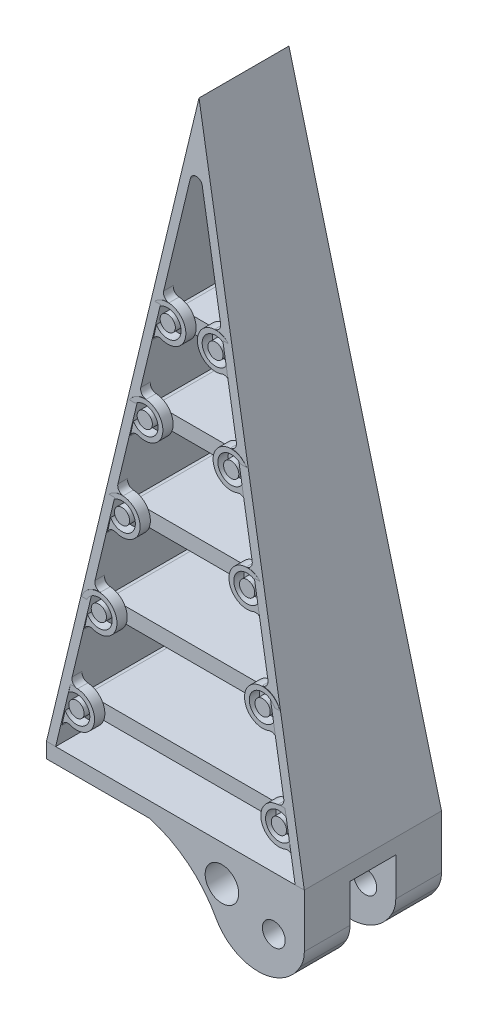
SolidWorks part; units mm, degrees
ref_plane "Ebene vorne" through (0, 0, 0) normal (0, 0, 1) x (1, 0, 0)
ref_plane "Ebene oben" through (0, 0, 0) normal (0, 1, 0) x (1, 0, 0)
ref_plane "Ebene rechts" through (0, 0, 0) normal (1, 0, 0) x (0, 0, -1)
ref_plane "Ebene7" through (0, 0, 9) normal (0, 0, 1) x (1, 0, 0)
ref_plane "Ebene8" through (17, 0, 0) normal (1, 0, 0) x (0, 0, -1)
sketch "Skizze1" plane through (0, 0, 0) normal (0, 0, 1) x (1, 0, 0)
  line L0 (0, 0) -> (16.9111, -80)
  line L1 (16.9111, -80) -> (15.7111, -80)
  line L2 (15.7111, -80) -> (0, -5.6767)
  line L3 (0, -5.6767) -> (-15.7111, -80)
  line L4 (-15.7111, -80) -> (-16.9111, -80)
  line L5 (-16.9111, -80) -> (0, 0)
  point P2 (-16.3111, -80)
  dimension "D1" = 1.2
  dimension "D2" = 1.2
  dimension "D3" = 23.872
  dimension "D4" = 80
extrude "Aufsatz-Linear austragen4" add sketch "Skizze1" along normal blind 18
sketch "Skizze11" plane through (17, 0, 0) normal (1, 0, 0) x (0, 0, -1)
  line L0 (-18, -80) -> (-14.9, 0)
  line L1 (-18, 0) -> (0, 0) construction
  line L2 (-14.9, 0) -> (-18, 0)
  line L3 (-18, 0) -> (-18, -80)
  line L4 (0, -80) -> (-3.1, 0)
  line L5 (-3.1, 0) -> (0, 0)
  line L6 (0, 0) -> (0, -80)
  dimension "D1" = 3.1
  dimension "D2" = 3.1
extrude "Schnitt-Linear austragen1" cut sketch "Skizze11" against normal through all
sketch "Skizze6" plane through (0, 0, 9) normal (0, 0, 1) x (1, 0, 0)
  line L1 (0, -5.6767) -> (-15.7111, -80) construction
  line L2 (15.7111, -80) -> (0, -5.6767) construction
  line L8 (3.1325, -25.6767) -> (-3.1325, -25.6767)
  line L11 (-3.1325, -27.6767) -> (3.1325, -27.6767)
  arc A0 (-3.1325, -25.6767) -> (-3.1325, -27.6767) centre (-3.1325, -26.6767) ccw
  arc A1 (3.1325, -25.6767) -> (3.1325, -27.6767) centre (3.1325, -26.6767) cw
  point P4 (-4.1325, -26.6767)
  point P9 (4.1325, -26.6767)
  dimension "D3" = 0.3
  dimension "D1" = 20
  dimension "D2" = 2
  dimension "D4" = 0.3
extrude "Aufsatz-Linear austragen5" add sketch "Skizze6" along normal blind 5.37 and the other way blind 5.37
sketch "Skizze7" plane through (0, 0, 9) normal (0, 0, 1) x (1, 0, 0)
  line L9 (5.6692, -37.6767) -> (-5.6692, -37.6767)
  line L12 (-5.6692, -39.6767) -> (5.6692, -39.6767)
  line L13 (-3.1325, -27.6767) -> (3.1325, -27.6767) construction
  line L14 (0, -5.6767) -> (-15.7111, -80) construction
  line L15 (15.7111, -80) -> (0, -5.6767) construction
  arc A0 (-5.6692, -37.6767) -> (-5.6692, -39.6767) centre (-5.6692, -38.6767) ccw
  arc A1 (5.6692, -37.6767) -> (5.6692, -39.6767) centre (5.6692, -38.6767) cw
  point P3 (-6.6692, -38.6767)
  point P10 (6.6692, -38.6767)
  dimension "D3" = 0.3
  dimension "D1" = 10
  dimension "D2" = 2
  dimension "D4" = 0.3
extrude "Aufsatz-Linear austragen6" add sketch "Skizze7" along normal blind 5.85 and the other way blind 5.85
sketch "Skizze8" plane through (0, 0, 9) normal (0, 0, 1) x (1, 0, 0)
  line L9 (8.2059, -49.6767) -> (-8.2059, -49.6767)
  line L12 (-8.2059, -51.6767) -> (8.2059, -51.6767)
  line L13 (-5.6692, -39.6767) -> (5.6692, -39.6767) construction
  line L14 (0, -5.6767) -> (-15.7111, -80) construction
  line L15 (15.7111, -80) -> (0, -5.6767) construction
  arc A0 (-8.2059, -49.6767) -> (-8.2059, -51.6767) centre (-8.2059, -50.6767) ccw
  arc A1 (8.2059, -49.6767) -> (8.2059, -51.6767) centre (8.2059, -50.6767) cw
  point P6 (-9.2059, -50.6767)
  point P11 (9.2059, -50.6767)
  dimension "D3" = 0.3
  dimension "D1" = 10
  dimension "D2" = 2
  dimension "D4" = 0.3
extrude "Aufsatz-Linear austragen7" add sketch "Skizze8" along normal blind 6.3 and the other way blind 6.3
sketch "Skizze9" plane through (0, 0, 9) normal (0, 0, 1) x (1, 0, 0)
  line L9 (10.7426, -61.6767) -> (-10.7426, -61.6767)
  line L12 (-10.7426, -63.6767) -> (10.7426, -63.6767)
  line L13 (-8.2059, -51.6767) -> (8.2059, -51.6767) construction
  line L14 (0, -5.6767) -> (-15.7111, -80) construction
  line L15 (15.7111, -80) -> (0, -5.6767) construction
  arc A0 (-10.7426, -61.6767) -> (-10.7426, -63.6767) centre (-10.7426, -62.6767) ccw
  arc A1 (10.7426, -61.6767) -> (10.7426, -63.6767) centre (10.7426, -62.6767) cw
  point P3 (-11.7426, -62.6767)
  point P10 (11.7426, -62.6767)
  dimension "D3" = 0.3
  dimension "D1" = 10
  dimension "D2" = 2
  dimension "D4" = 0.3
extrude "Aufsatz-Linear austragen8" add sketch "Skizze9" along normal blind 6.8 and the other way blind 6.8
sketch "Skizze10" plane through (0, 0, 9) normal (0, 0, 1) x (1, 0, 0)
  line L9 (13.2792, -73.6767) -> (-13.2792, -73.6767)
  line L12 (-13.2792, -75.6767) -> (13.2792, -75.6767)
  line L13 (-10.7426, -63.6767) -> (10.7426, -63.6767) construction
  line L14 (0, -5.6767) -> (-15.7111, -80) construction
  line L15 (15.7111, -80) -> (0, -5.6767) construction
  arc A0 (-13.2792, -73.6767) -> (-13.2792, -75.6767) centre (-13.2792, -74.6767) ccw
  arc A1 (13.2792, -73.6767) -> (13.2792, -75.6767) centre (13.2792, -74.6767) cw
  point P3 (-14.2792, -74.6767)
  point P10 (14.2792, -74.6767)
  dimension "D3" = 0.3
  dimension "D1" = 10
  dimension "D2" = 2
  dimension "D4" = 0.3
extrude "Aufsatz-Linear austragen9" add sketch "Skizze10" along normal blind 7.2 and the other way blind 7.2
sketch "Skizze13" plane through (0, 0, 14.37) normal (0, 0, 1) x (1, 0, 0)
  circle A0 centre (-3.1325, -26.6767) radius 1
  circle A1 centre (3.1325, -26.6767) radius 1
  dimension "D1" = 2
  dimension "D2" = 2
extrude "Aufsatz-Linear austragen12" add sketch "Skizze13" along normal blind 1.5
sketch "Skizze15" plane through (0, 0, 15.3) normal (0, 0, 1) x (1, 0, 0)
  circle A0 centre (-8.2059, -50.6767) radius 1
  circle A1 centre (8.2059, -50.6767) radius 1
extrude "Aufsatz-Linear austragen14" add sketch "Skizze15" along normal blind 1.5
sketch "Skizze14" plane through (0, 0, 14.85) normal (0, 0, 1) x (1, 0, 0)
  circle A0 centre (-5.6692, -38.6767) radius 1
  circle A1 centre (5.6692, -38.6767) radius 1
extrude "Aufsatz-Linear austragen13" add sketch "Skizze14" along normal blind 1.5
sketch "Skizze16" plane through (0, 0, 15.8) normal (0, 0, 1) x (1, 0, 0)
  circle A0 centre (-10.7426, -62.6767) radius 1
  circle A1 centre (10.7426, -62.6767) radius 1
extrude "Aufsatz-Linear austragen15" add sketch "Skizze16" along normal blind 1.5
sketch "Skizze17" plane through (0, 0, 16.2) normal (0, 0, 1) x (1, 0, 0)
  circle A0 centre (-13.2792, -74.6767) radius 1
  circle A1 centre (13.2792, -74.6767) radius 1
extrude "Aufsatz-Linear austragen16" add sketch "Skizze17" along normal blind 1.5
sketch "Skizze18" plane through (0, 0, 3.63) normal (0, 0, -1) x (-1, 0, 0)
  circle A0 centre (-3.1325, -26.6767) radius 1
  circle A1 centre (3.1325, -26.6767) radius 1
extrude "Aufsatz-Linear austragen17" add sketch "Skizze18" along normal blind 1.5
sketch "Skizze19" plane through (0, 0, 3.15) normal (0, 0, -1) x (-1, 0, 0)
  circle A0 centre (-5.6692, -38.6767) radius 1
  circle A1 centre (5.6692, -38.6767) radius 1
extrude "Aufsatz-Linear austragen18" add sketch "Skizze19" along normal blind 1.5
sketch "Skizze20" plane through (0, 0, 2.7) normal (0, 0, -1) x (-1, 0, 0)
  circle A0 centre (-8.2059, -50.6767) radius 1
  circle A1 centre (8.2059, -50.6767) radius 1
extrude "Aufsatz-Linear austragen19" add sketch "Skizze20" along normal blind 1.5
sketch "Skizze21" plane through (0, 0, 2.2) normal (0, 0, -1) x (-1, 0, 0)
  circle A0 centre (-10.7426, -62.6767) radius 1
  circle A1 centre (10.7426, -62.6767) radius 1
extrude "Aufsatz-Linear austragen20" add sketch "Skizze21" along normal blind 1.5
sketch "Skizze22" plane through (0, 0, 1.8) normal (0, 0, -1) x (-1, 0, 0)
  circle A0 centre (-13.2792, -74.6767) radius 1
  circle A1 centre (13.2792, -74.6767) radius 1
extrude "Aufsatz-Linear austragen21" add sketch "Skizze22" along normal blind 1.5
sketch "Skizze24" plane through (0, 0, 15.87) normal (0, 0, 1) x (1, 0, 0)
  circle A0 centre (-3.1325, -26.6767) radius 1.75
  circle A1 centre (-3.1325, -26.6767) radius 2.375
  circle A2 centre (3.1325, -26.6767) radius 1.75
  circle A3 centre (3.1325, -26.6767) radius 2.375
  dimension "D1" = 3.5
  dimension "D2" = 4.75
  dimension "D3" = 3.5
  dimension "D4" = 4.75
extrude "Aufsatz-Linear austragen22" add sketch "Skizze24" against normal blind 1.35
sketch "Skizze25" plane through (0, 0, 16.35) normal (0, 0, 1) x (1, 0, 0)
  circle A0 centre (-5.6692, -38.6767) radius 1.75
  circle A1 centre (-5.6692, -38.6767) radius 2.375
  circle A2 centre (5.6692, -38.6767) radius 1.75
  circle A3 centre (5.6692, -38.6767) radius 2.375
  dimension "D1" = 3.5
  dimension "D2" = 4.75
  dimension "D3" = 3.5
  dimension "D4" = 4.75
extrude "Aufsatz-Linear austragen23" add sketch "Skizze25" against normal blind 1.35
sketch "Skizze26" plane through (0, 0, 16.8) normal (0, 0, 1) x (1, 0, 0)
  circle A0 centre (-8.2059, -50.6767) radius 1.75
  circle A1 centre (-8.2059, -50.6767) radius 2.375
  circle A2 centre (8.2059, -50.6767) radius 1.75
  circle A3 centre (8.2059, -50.6767) radius 2.375
  dimension "D1" = 3.5
  dimension "D2" = 4.75
  dimension "D3" = 3.5
  dimension "D4" = 4.75
extrude "Aufsatz-Linear austragen24" add sketch "Skizze26" against normal blind 1.35
sketch "Skizze27" plane through (0, 0, 17.3) normal (0, 0, 1) x (1, 0, 0)
  circle A0 centre (-10.7426, -62.6767) radius 1.75
  circle A1 centre (-10.7426, -62.6767) radius 2.375
  circle A2 centre (10.7426, -62.6767) radius 1.75
  circle A3 centre (10.7426, -62.6767) radius 2.375
  dimension "D1" = 3.5
  dimension "D2" = 4.75
  dimension "D3" = 3.5
  dimension "D4" = 4.75
extrude "Aufsatz-Linear austragen25" add sketch "Skizze27" against normal blind 1.35
sketch "Skizze28" plane through (0, 0, 17.7) normal (0, 0, 1) x (1, 0, 0)
  circle A0 centre (-13.2792, -74.6767) radius 1.75
  circle A1 centre (-13.2792, -74.6767) radius 2.375
  circle A2 centre (13.2792, -74.6767) radius 1.75
  circle A3 centre (13.2792, -74.6767) radius 2.375
  dimension "D1" = 3.5
  dimension "D2" = 4.75
  dimension "D3" = 3.5
  dimension "D4" = 4.75
extrude "Aufsatz-Linear austragen26" add sketch "Skizze28" against normal blind 1.35
sketch "Skizze29" plane through (0, 0, 2.13) normal (0, 0, -1) x (-1, 0, 0)
  circle A0 centre (-3.1325, -26.6767) radius 1.75
  circle A1 centre (-3.1325, -26.6767) radius 2.375
  circle A2 centre (3.1325, -26.6767) radius 1.75
  circle A3 centre (3.1325, -26.6767) radius 2.375
extrude "Aufsatz-Linear austragen27" add sketch "Skizze29" against normal blind 1.35
sketch "Skizze30" plane through (0, 0, 1.65) normal (0, 0, -1) x (-1, 0, 0)
  circle A0 centre (-5.6692, -38.6767) radius 1.75
  circle A1 centre (-5.6692, -38.6767) radius 2.375
  circle A2 centre (5.6692, -38.6767) radius 1.75
  circle A3 centre (5.6692, -38.6767) radius 2.375
extrude "Aufsatz-Linear austragen28" add sketch "Skizze30" against normal blind 1.35
sketch "Skizze31" plane through (0, 0, 1.2) normal (0, 0, -1) x (-1, 0, 0)
  circle A0 centre (-8.2059, -50.6767) radius 1.75
  circle A1 centre (-8.2059, -50.6767) radius 2.375
  circle A2 centre (8.2059, -50.6767) radius 1.75
  circle A3 centre (8.2059, -50.6767) radius 2.375
extrude "Aufsatz-Linear austragen29" add sketch "Skizze31" against normal blind 1.35
sketch "Skizze32" plane through (0, 0, 0.7) normal (0, 0, -1) x (-1, 0, 0)
  circle A0 centre (-10.7426, -62.6767) radius 1.75
  circle A1 centre (-10.7426, -62.6767) radius 2.375
  circle A2 centre (10.7426, -62.6767) radius 1.75
  circle A3 centre (10.7426, -62.6767) radius 2.375
extrude "Aufsatz-Linear austragen30" add sketch "Skizze32" against normal blind 1.35
sketch "Skizze33" plane through (0, 0, 0.3) normal (0, 0, -1) x (-1, 0, 0)
  circle A0 centre (-13.2792, -74.6767) radius 1.75
  circle A1 centre (-13.2792, -74.6767) radius 2.375
  circle A2 centre (13.2792, -74.6767) radius 1.75
  circle A3 centre (13.2792, -74.6767) radius 2.375
extrude "Aufsatz-Linear austragen31" add sketch "Skizze33" against normal blind 1.35
fillet "Verrundung1" radius 0.8 1 edges at (0, -5.6767, 9)
fillet "Verrundung2" radius 0.8 40 edges at (12.4073, -64.3707, 16.625) (9.8706, -52.3707, 16.125) (7.3339, -40.3707, 15.675) (4.7973, -28.3707, 15.195) (-4.7973, -28.3707, 15.195) (-7.3339, -40.3707, 15.675) (-9.8706, -52.3707, 16.125) (-12.4073, -64.3707, 16.625) (-14.9439, -76.3707, 17.025) (14.9439, -76.3707, 17.025) (14.116, -72.454, 17.025) (-14.116, -72.454, 17.025) (-11.5793, -60.454, 16.5963) (11.5793, -60.454, 16.5963) (9.0427, -48.454, 16.1138) (-9.0427, -48.454, 16.1138) (-6.506, -36.454, 15.6563) (6.506, -36.454, 15.6563) (3.9693, -24.454, 15.1838) (-3.9693, -24.454, 15.1838) (-7.3339, -40.3707, 2.325) (-4.7973, -28.3707, 2.805) (-3.9693, -24.454, 2.8162) (-6.506, -36.454, 2.3437) (-9.0427, -48.454, 1.8862) (-9.8706, -52.3707, 1.875) (-12.4073, -64.3707, 1.375) (-11.5793, -60.454, 1.4037) (-14.116, -72.454, 0.975) (-14.9439, -76.3707, 0.975) (14.9439, -76.3707, 0.975) (14.116, -72.454, 0.975) (12.4073, -64.3707, 1.375) (11.5793, -60.454, 1.4037) (9.8706, -52.3707, 1.875) (9.0427, -48.454, 1.8862) (7.3339, -40.3707, 2.325) (6.506, -36.454, 2.3437) (4.7973, -28.3707, 2.805) (3.9693, -24.454, 2.8162)
sketch "Skizze37" plane through (0, -80, 0) normal (0, -1, 0) x (1, 0, 0)
  line L0 (-16.9111, 0) -> (-15.7111, 0)
  line L1 (-15.7111, 0) -> (16.9111, 0)
  line L2 (16.9111, 0) -> (16.9111, 18)
  line L3 (16.9111, 18) -> (-16.9111, 18)
  line L4 (-16.9111, 18) -> (-16.9111, 0)
extrude "Aufsatz-Linear austragen32" add sketch "Skizze37" along normal blind 2
sketch "Skizze38" plane through (0, 0, 18) normal (0, 0, 1) x (1, 0, 0)
  line L0 (16.9111, -82) -> (6.7313, -82)
  line L1 (16.9111, -82) -> (16.9111, -87)
  line L2 (16.9111, -82) -> (-16.9111, -82) construction
  line L3 (16.9111, -82) -> (16.9111, -80) construction
  circle A0 centre (12.9111, -87) radius 4
  circle A1 centre (12.9111, -87) radius 1.5
  arc A2 (-3.3949, -82) -> (5.3134, -88.966) centre (-7.2601, -95.7582) cw
  arc A4 (5.3134, -88.966) -> (16.3947, -88.966) centre (10.8541, -85.9729) ccw
  line M6 (-16.9111, -82) -> (16.9111, -82)
  dimension "D1" = 3
  dimension "D2" = 5
  dimension "D3" = 8
extrude "Aufsatz-Linear austragen34" add sketch "Skizze38" against normal blind 18 contours A0 L1 M6 | A0 A1 region at (7.5381, -85.6971, 18) region at (16.6704, -87.9876, 18)
sketch "Skizze39" plane through (0, 0, 18) normal (0, 0, 1) x (1, 0, 0)
  circle A1 centre (12.9111, -87) radius 4
  circle A2 centre (12.9111, -87) radius 1.5 construction
extrude "Schnitt-Linear austragen2" cut sketch "Skizze39" against normal blind 6 from offset 6 offset against normal yes
sketch "Skizze40" plane through (-16.9111, 0, 0) normal (-1, 0, 0) x (0, 0, 1)
  line L7 (12, -93.7115) -> (6, -93.7115)
  line L9 (12, -93.7115) -> (12, -82)
  line L10 (18, -82) -> (0, -82) construction
  line L11 (12, -82) -> (6, -82)
  line L12 (6, -82) -> (6, -93.7115)
extrude "Schnitt-Linear austragen3" cut sketch "Skizze40" against normal blind 43.6
sketch "Skizze41" plane through (0, 0, 0) normal (0, 0, -1) x (-1, 0, 0)
  line L0 (-6.1051, -82) -> (-6.1051, -84.7) construction
  line L1 (3.3949, -82) -> (-6.1051, -82) construction
  circle A0 centre (-6.1051, -84.7) radius 2.2
  dimension "D1" = 4.4
  dimension "D2" = 2.7
  dimension "D3" = 9.5
extrude "Schnitt-Linear austragen4" cut sketch "Skizze41" against normal through all
sketch "Skizze42" plane through (-16.9111, 0, 0) normal (-1, 0, 0) x (0, 0, 1)
  line L0 (8, -82) -> (9, -82)
  line L1 (18, -82) -> (0, -82) construction
  line L3 (9, -82) -> (9, -82.5253)
  line L4 (9, -82.5253) -> (8.82, -82.5253)
  line L5 (8, -82) -> (8, -82.5253)
  line L6 (8, -82.5253) -> (8.18, -82.5253)
  line L7 (8.5, -82) -> (8.5, -82.1718) construction
  arc A0 (8.5, -82.1718) -> (8.82, -82.5253) centre (8.5, -82.4934) cw
  arc A1 (8.5, -82.1718) -> (8.18, -82.5253) centre (8.5, -82.4934) ccw
  point P16 (9, -82)
  dimension "D1" = 1
  dimension "D2" = 0.18
  dimension "D3" = 0.18
extrude "Aufsatz-Linear austragen35" add sketch "Skizze42" against normal blind 25
